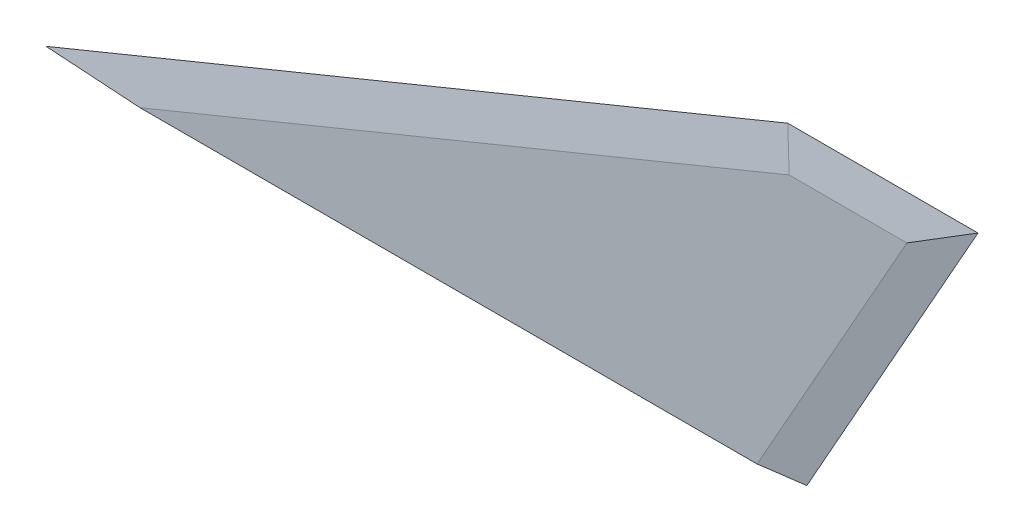
SolidWorks part; units mm, degrees
ref_plane "Front Plane" through (0, 0, 0) normal (0, 0, 1) x (1, 0, 0)
ref_plane "Top Plane" through (0, 0, 0) normal (0, 1, 0) x (1, 0, 0)
ref_plane "Right Plane" through (0, 0, 0) normal (1, 0, 0) x (0, 0, -1)
sketch "Sketch1" plane through (0, 0, 0) normal (0, 0, 1) x (1, 0, 0)
  line L0 (0, 0) -> (200, 0)
  line L1 (200, 0) -> (245, 80)
  line L2 (245, 80) -> (195, 80)
  line L3 (195, 80) -> (0, 0)
  dimension "D1" = 200
  dimension "D2" = 50
  dimension "D3" = 195
  dimension "D4" = 80
extrude "Boss-Extrude1" add sketch "Sketch1" along normal blind 3.18
chamfer "Chamfer1" distance 1.59 distance2 10 3 edges at (222.5, 40, 3.18) (97.5, 40, 3.18) (220, 80, 3.18) first distance on face at (222.5, 40, 1.59) first distance on face at (97.5, 40, 1.59) first distance on face at (220, 80, 1.59)
chamfer "Chamfer2" distance 10 distance2 1.59 3 edges at (222.5, 40, 0) (97.5, 40, 0) (220, 80, 0) first distance on face at (160, 40, 0)
sketch "Sketch2" plane through (0, 0, 0) normal (1, 0, 0) x (0, 0, -1)
  circle A0 centre (-1.59, -40.9692) radius 41
  dimension "D1" = 82
extrude "Cut-Extrude1" cut sketch "Sketch2" along normal blind 200
